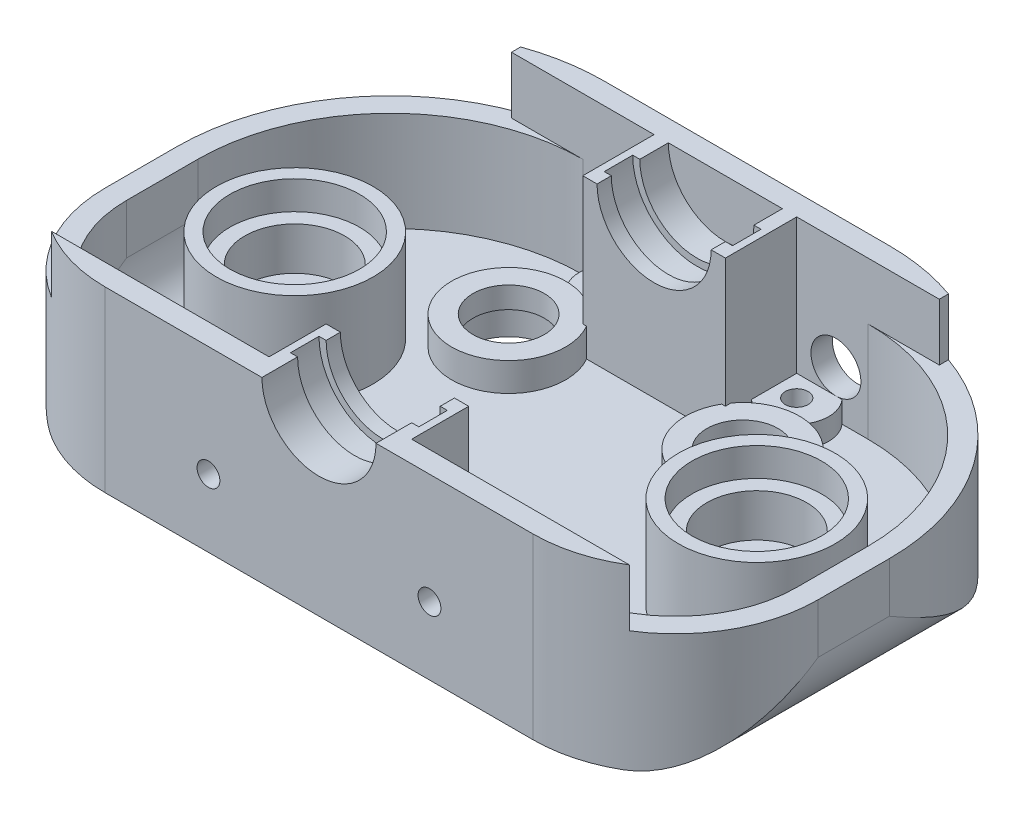
SolidWorks part; units mm, degrees
ref_plane "Front Plane" through (0, 0, 0) normal (0, 0, 1) x (1, 0, 0)
ref_plane "Top Plane" through (0, 0, 0) normal (0, 1, 0) x (1, 0, 0)
ref_plane "Right Plane" through (0, 0, 0) normal (1, 0, 0) x (0, 0, -1)
other "Configuration Table"
sketch "草图1" plane through (0, 0, 0) normal (0, 1, 0) x (1, 0, 0)
  line L5 (-50, 30) -> (50, 30)
  line L6 (-50, 30) -> (-50, -30)
  line L7 (-50, -30) -> (50, -30)
  line L8 (50, 30) -> (50, -30)
  line L9 (-50, 30) -> (50, -30) construction
  line L10 (-50, -30) -> (50, 30) construction
  point P0 (0, 0)
  dimension "D1" = 100
  dimension "D2" = 60
extrude "凸台-拉伸1" add sketch "草图1" along normal blind 25
fillet "圆角2" radius 10 2 edges at (50, 0, 0) (-50, 0, 0)
fillet "圆角1" radius 20 2 edges at (50, 17.5, 30) (-50, 17.5, 30)
fillet "圆角3" radius 30 2 edges at (50, 17.5, -30) (-50, 17.5, -30)
shell "抽壳1" thickness 3
sketch "草图2" plane through (0, 0, 27) normal (0, 0, -1) x (-1, 0, 0)
  line L0 (-20, 25) -> (20, 25) construction
  circle A0 centre (-15.5, 9.5) radius 1.6
  circle A1 centre (15.5, 9.5) radius 1.6
  dimension "D4" = 3.2
  dimension "D5" = 3.2
  dimension "D1" = 15.5
  dimension "D2" = 31
  dimension "D3" = 15.5
extrude "切除-拉伸1" cut sketch "草图2" against normal through all both and the other way through all
sketch "草图3" plane through (-50, 0, 0) normal (-1, 0, 0) x (0, 0, 1)
  line L0 (0, 25) -> (10, 25) construction
  line L1 (-27, 27.6853) -> (27, 27.6853)
  line L2 (-27, 27.6853) -> (-27, 17)
  line L3 (-27, 17) -> (27, 17)
  line L4 (27, 27.6853) -> (27, 17)
  line L6 (-30, 25) -> (-30, 10) construction
  line L7 (30, 25) -> (30, 0) construction
  dimension "D1" = 8
  dimension "D2" = 3
  dimension "D3" = 3
extrude "切除-拉伸2" cut sketch "草图3" against normal through all
sketch "草图5" plane through (0, 0, 27) normal (0, 0, -1) x (-1, 0, 0)
  line L0 (-20, 25) -> (20, 25) construction
  line L1 (-10, 25) -> (10, 25)
  line L2 (-10, 25) -> (-10, 3)
  line L3 (-10, 3) -> (10, 3)
  line L4 (10, 25) -> (10, 3)
  line L5 (-20, 0) -> (20, 0) construction
  dimension "D1" = 3
  dimension "D2" = 20
  dimension "D3" = 10
extrude "凸台-拉伸3" add sketch "草图5" along normal up to surface (54 mm away)
sketch "草图6" plane through (0, 25, 0) normal (0, 1, 0) x (1, 0, 0)
  line L0 (-10, 27) -> (-10, -27) construction
  line L1 (-10, 17) -> (10, 17)
  line L2 (-10, 17) -> (-10, -19)
  line L3 (-10, -19) -> (10, -19)
  line L4 (10, 17) -> (10, -19)
  line L5 (10, 27) -> (10, -27) construction
  line L6 (-30, -27) -> (-10, -27) construction
  line L7 (10, -27) -> (40.5357, -27) construction
  dimension "D1" = 8
  dimension "D2" = 44
extrude "切除-拉伸4" cut sketch "草图6" against normal up to surface (22 mm away) up to face at (-25.1992, 3, 0.7143)
sketch "草图7" plane through (0, 0, 30) normal (0, 0, 1) x (1, 0, 0)
  line L0 (-30, 25) -> (30, 25) construction
  circle A0 centre (0, 25) radius 8
  dimension "D1" = 16
extrude "切除-拉伸5" cut sketch "草图7" against normal up to surface (57 mm away)
ref_plane "基准面1" through (0, 0, 25) normal (0, 0, -1) x (-1, 0, 0)
sketch "草图8" plane through (0, 0, 25) normal (0, 0, -1) x (-1, 0, 0)
  line L0 (-20, 25) -> (20, 25) construction
  circle A0 centre (0, 25) radius 9
  dimension "D1" = 18
extrude "切除-拉伸6" cut sketch "草图8" along normal blind 4
ref_plane "基准面2" through (0, 0, -19) normal (0, 0, 1) x (1, 0, 0)
sketch "草图9" plane through (0, 0, -19) normal (0, 0, 1) x (1, 0, 0)
  line L0 (-8, 25) -> (8, 25) construction
  circle A0 centre (0, 25) radius 9
  dimension "D1" = 18
extrude "切除-拉伸7" cut sketch "草图9" against normal blind 4
sketch "草图11" plane through (0, 3, 0) normal (0, 1, 0) x (1, 0, 0)
  line L0 (8, -30) -> (30, -30) construction
  circle A0 centre (-32.4, -1) radius 11
  circle A1 centre (32.4, -1) radius 11
  dimension "D4" = 22
  dimension "D5" = 22
  dimension "D1" = 64.8
  dimension "D2" = 32.4
  dimension "D3" = 29
extrude "凸台-拉伸4" add sketch "草图11" along normal blind 13
sketch "草图12" plane through (0, 16, 0) normal (0, 1, 0) x (1, 0, 0)
  circle A0 centre (-32.4, -1) radius 9.1
  circle A1 centre (32.4, -1) radius 9.1
  dimension "D1" = 18.2
  dimension "D2" = 18.2
extrude "切除-拉伸8" cut sketch "草图12" against normal blind 4
sketch "草图13" plane through (0, 12, 0) normal (0, 1, 0) x (1, 0, 0)
  circle A0 centre (-32.4, -1) radius 7
  circle A1 centre (32.4, -1) radius 7
  dimension "D1" = 14
  dimension "D2" = 14
extrude "切除-拉伸9" cut sketch "草图13" against normal blind 6
sketch "草图14" plane through (0, 3, 0) normal (0, 1, 0) x (1, 0, 0)
  line L0 (10, -27) -> (40.5357, -27) construction
  circle A1 centre (13, -22) radius 4.5
  circle A2 centre (-13, -22) radius 4.5
  circle A3 centre (-13, 24) radius 4.5
  circle A4 centre (13, 24) radius 4.5
  dimension "D1" = 13
  dimension "D2" = 9
  dimension "D3" = 5
  dimension "D4" = 2
  dimension "D5" = 2
extrude "凸台-拉伸6" add sketch "草图14" along normal blind 3
sketch "草图16" plane through (0, 6, 0) normal (0, 1, 0) x (1, 0, 0)
  circle A0 centre (13, -22) radius 1.6
  circle A1 centre (-13, -22) radius 1.6
  circle A2 centre (-13, 24) radius 1.6
  circle A3 centre (13, 24) radius 1.6
  dimension "D1" = 3.2
  dimension "D2" = 3.2
  dimension "D3" = 3.2
  dimension "D4" = 3.2
extrude "切除-拉伸13" cut sketch "草图16" against normal through all
sketch "草图18" plane through (0, 0, -30) normal (0, 0, -1) x (-1, 0, 0)
  line L1 (-50, 25) -> (-30, 25)
  line L2 (-50, 25) -> (-50, 17)
  line L3 (-50, 17) -> (-30, 17)
  line L4 (-30, 25) -> (-30, 17)
  line L5 (50, 25) -> (30, 25)
  line L6 (50, 25) -> (50, 17)
  line L7 (50, 17) -> (30, 17)
  line L8 (30, 25) -> (30, 17)
  dimension "D1" = 8
  dimension "D2" = 20
  dimension "D3" = 8
  dimension "D4" = 20
extrude "切除-拉伸15" cut sketch "草图18" against normal blind 10
sketch "草图20" plane through (0, 6, 0) normal (0, 1, 0) x (1, 0, 0)
  circle A0 centre (-32.4, -1) radius 1.6
  circle A1 centre (32.4, -1) radius 1.6
  dimension "D1" = 3.2
  dimension "D2" = 3.2
extrude "切除-拉伸16" cut sketch "草图20" against normal blind 10
sketch "草图21" plane through (0, 0, 0) normal (0, -1, 0) x (1, 0, 0)
  circle A0 centre (16.4, -13) radius 8
  circle A1 centre (-16.4, -13) radius 8
  point P0 (32.4, 1)
  point P1 (16.4, -13)
  dimension "D3" = 16
  dimension "D4" = 16
  dimension "D1" = 16
  dimension "D2" = 14
  dimension "D5" = 32.8
extrude "凸台-拉伸7" add sketch "草图21" against normal blind 7
sketch "草图25" plane through (0, 7, 0) normal (0, 1, 0) x (1, 0, 0)
  circle A0 centre (-16.4, 13) radius 5
  circle A1 centre (16.4, 13) radius 5
  dimension "D1" = 10
  dimension "D2" = 10
extrude "切除-拉伸19" cut sketch "草图25" against normal through all both and the other way through all
sketch "草图26" plane through (0, 0, 0) normal (0, -1, 0) x (1, 0, 0)
  circle A0 centre (-16.4, -13) radius 6
  circle A1 centre (16.4, -13) radius 6
  dimension "D1" = 12
  dimension "D2" = 12
extrude "切除-拉伸20" cut sketch "草图26" against normal blind 4
sketch "草图27" plane through (0, 0, -30) normal (0, 0, -1) x (-1, 0, 0)
  circle A0 centre (-15.5, 9.5) radius 3.5
  circle A1 centre (15.5, 9.5) radius 3.5
  dimension "D1" = 7
  dimension "D2" = 7
extrude "切除-拉伸21" cut sketch "草图27" against normal mid plane 10
sketch "草图17" plane through (0, 0, 0) normal (0, -1, 0) x (1, 0, 0)
  circle A0 centre (-13, 22) radius 3
  circle A1 centre (13, 22) radius 3
  circle A2 centre (13, -24) radius 3
  circle A3 centre (-13, -24) radius 3
  circle A4 centre (-32.4, 1) radius 3
  circle A5 centre (32.4, 1) radius 3
  dimension "D1" = 6
  dimension "D2" = 6
  dimension "D3" = 6
  dimension "D4" = 6
  dimension "D5" = 6
  dimension "D6" = 6
extrude "切除-拉伸14" cut sketch "草图17" against normal blind 3
